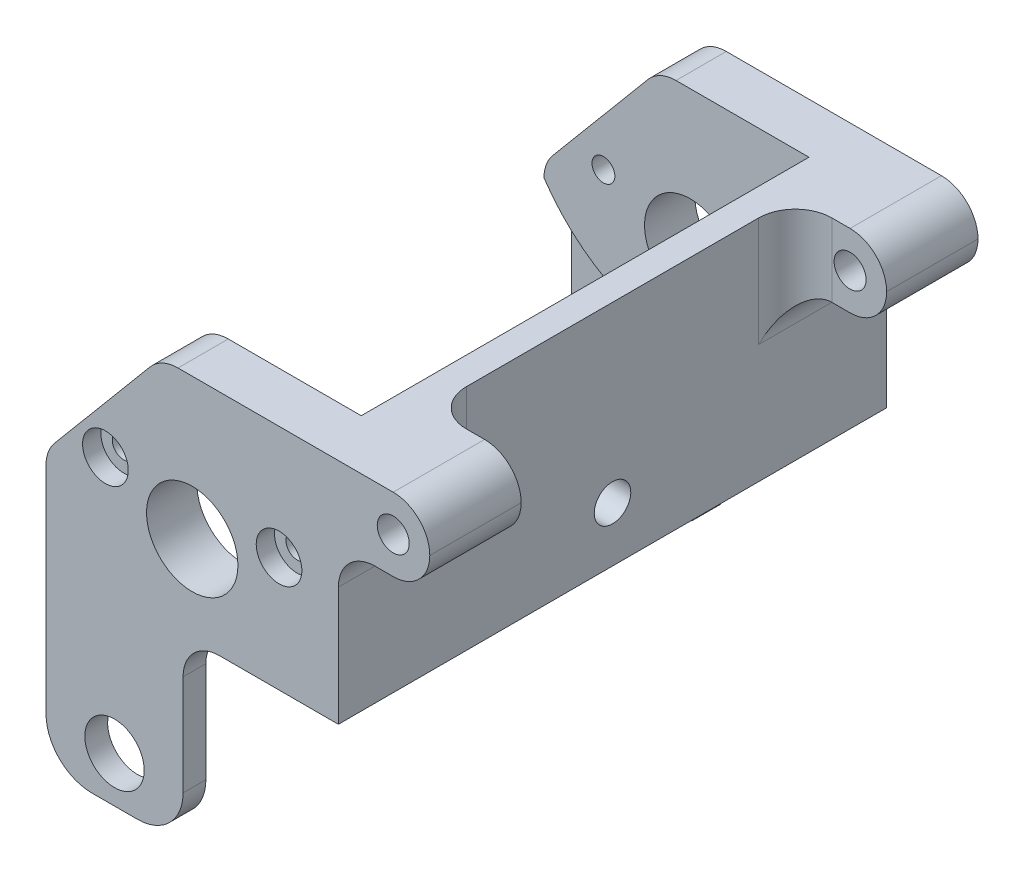
SolidWorks part; units mm, degrees
ref_plane "Front Plane" through (0, 0, 0) normal (0, 0, 1) x (1, 0, 0)
ref_plane "Top Plane" through (0, 0, 0) normal (0, 1, 0) x (1, 0, 0)
ref_plane "Right Plane" through (0, 0, 0) normal (1, 0, 0) x (0, 0, -1)
sketch "Sketch2" plane through (0, 0, 0) normal (0, 0, 1) x (1, 0, 0)
  line L0 (-7.5, 5) -> (-7.5, 30)
  line L1 (-7.5, 30) -> (5.0865, 45)
  line L2 (5.0865, 45) -> (24.5, 45)
  line L3 (24.5, 45) -> (24.5, 20)
  line L4 (24.5, 20) -> (7.5, 20)
  line L5 (7.5, 20) -> (7.5, 5)
  line L6 (-2.5, 0) -> (2.5, 0)
  line L7 (-7.5, 0) -> (7.5, 0) construction
  line L8 (-7.5, 5) -> (7.5, 5) construction
  line L9 (18.0048, 32.5697) -> (-0.9952, 32.5697) construction
  line L10 (8.5048, 32.5697) -> (8.5048, 29.5697) construction
  line L11 (0, 5) -> (8.5048, 29.5697) construction
  circle A5 centre (0, 5) radius 3.25
  circle A6 centre (18.0048, 32.5697) radius 1.25
  circle A7 centre (-0.9952, 32.5697) radius 1.25
  circle A8 centre (8.5048, 29.5697) radius 5
  circle A9 centre (8.5048, 32.5697) radius 12.5 construction
  arc A10 (2.5, 0) -> (7.5, 5) centre (2.5, 5) ccw
  arc A11 (-7.5, 5) -> (-2.5, 0) centre (-2.5, 5) ccw
  dimension "D3" = 6.5
  dimension "D4" = 5
  dimension "D10" = 10
  dimension "D12" = 2.5
  dimension "D14" = 25
  dimension "D15" = 5
  dimension "D1" = 40
  dimension "D2" = 15
  dimension "D5" = 30
  dimension "D6" = 15
  dimension "D7" = 17
  dimension "D8" = 20
  dimension "D9" = 19
  dimension "D11" = 3
  dimension "D13" = 26
extrude "Boss-Extrude1" add sketch "Sketch2" along normal blind 30 and the other way blind 30
sketch "Sketch3" plane through (0, 45, 0) normal (0, 1, 0) x (1, 0, 0)
  line L0 (-7.5, -30) -> (-7.5, 30) construction
  line L1 (-36.5, -27.5) -> (21.5, -27.5)
  line L2 (-36.5, -27.5) -> (-36.5, 27.5)
  line L3 (-36.5, 27.5) -> (21.5, 27.5)
  line L4 (21.5, -27.5) -> (21.5, 27.5)
  line L5 (-36.5, -27.5) -> (21.5, 27.5) construction
  line L6 (-36.5, 27.5) -> (21.5, -27.5) construction
  line L7 (24.5, 30) -> (5.0865, 30) construction
  line L8 (24.5, -30) -> (24.5, 30) construction
  point P0 (-7.5, 0)
  dimension "D1" = 2.5
  dimension "D2" = 3
extrude "Cut-Extrude1" cut sketch "Sketch3" against normal through all
sketch "Sketch4" plane through (24.5, 0, 0) normal (1, 0, 0) x (0, 0, -1)
  line L1 (-30, 45) -> (-20, 45)
  line L2 (-30, 45) -> (-30, 37)
  line L3 (-30, 37) -> (-20, 37)
  line L4 (-20, 45) -> (-20, 37)
  dimension "D1" = 10
  dimension "D2" = 8
extrude "Boss-Extrude2" add sketch "Sketch4" along normal blind 10
fillet "Fillet1" radius 4 2 edges at (34.5, 37, 25) (34.5, 45, 25)
sketch "Sketch5" plane through (0, 0, 20) normal (0, 0, -1) x (-1, 0, 0)
  circle A0 centre (-30.5, 41) radius 1.75
  dimension "D1" = 3.5
extrude "Cut-Extrude2" cut sketch "Sketch5" against normal through all
mirror "Mirror1" about plane through (0, 0, 0) normal (0, 0, 1) of "Cut-Extrude2", "Fillet1", "Boss-Extrude2"
fillet "Fillet2" radius 4 10 edges at (24.5, 41, -20) (24.5, 41, 20) (5.0865, 45, -28.75) (7.5, 20, -28.75) (24.5, 37, -25) (24.5, 37, 25) (7.5, 20, 28.75) (5.0865, 45, 28.75) (-7.5, 30, 28.75) (-7.5, 30, -28.75)
sketch "Sketch6" plane through (0, 0, -27.5) normal (0, 0, 1) x (1, 0, 0)
  line L0 (-0.9952, 32.5697) -> (18.0048, 32.5697) construction
  line L7 (21.5, 45) -> (6.9517, 45)
  line L8 (3.8875, 43.5712) -> (-6.5642, 31.1153)
  line L9 (-7.5, 28.5441) -> (-7.5, 5)
  line L10 (-2.5, 0) -> (2.5, 0)
  line L11 (7.5, 5) -> (7.5, 16)
  line L12 (11.5, 20) -> (21.5, 20)
  line L13 (21.5, 20) -> (21.5, 45)
  line L14 (21.5, 45) -> (6.9517, 45)
  line L15 (3.8875, 43.5712) -> (-6.5642, 31.1153)
  line L19 (11.5, 20) -> (21.5, 20)
  line L20 (21.5, 20) -> (21.5, 45)
  arc A1 (11.5, 20) -> (-7.5, 28.5441) centre (8.8465, 39.497) cw
  circle A2 centre (18.0048, 32.5697) radius 1.25 construction
  circle A3 centre (8.5048, 29.5697) radius 5 construction
  circle A4 centre (-0.9952, 32.5697) radius 1.25 construction
  circle A5 centre (18.0048, 32.5697) radius 1.25
  arc A6 (6.9517, 45) -> (3.8875, 43.5712) centre (6.9517, 41) ccw
  arc A7 (-6.5642, 31.1153) -> (-7.5, 28.5441) centre (-3.5, 28.5441) ccw
  arc A8 (-7.5, 5) -> (-2.5, 0) centre (-2.5, 5) ccw
  arc A9 (2.5, 0) -> (7.5, 5) centre (2.5, 5) ccw
  arc A10 (11.5, 20) -> (7.5, 16) centre (11.5, 16) ccw
  arc A11 (6.9517, 45) -> (3.8875, 43.5712) centre (6.9517, 41) ccw
  arc A12 (-6.5642, 31.1153) -> (-7.5, 28.5441) centre (-3.5, 28.5441) ccw
  circle A16 centre (8.5048, 29.5697) radius 5
  circle A17 centre (-0.9952, 32.5697) radius 1.25
  dimension "D1" = 0
extrude "Boss-Extrude3" add sketch "Sketch6" along normal blind 3
sketch "Sketch7" plane through (0, 0, -30) normal (0, 0, -1) x (-1, 0, 0)
  circle A0 centre (-18.0048, 32.5697) radius 2.5
  circle A1 centre (0.9952, 32.5697) radius 2.5
  dimension "D1" = 5
extrude "Cut-Extrude3" cut sketch "Sketch7" against normal blind 2
mirror "Mirror2" about plane through (0, 0, 0) normal (0, 0, 1) of "Cut-Extrude3", "Boss-Extrude3"
sketch "Sketch8" plane through (21.5, 0, 0) normal (-1, 0, 0) x (0, 0, 1)
  line L0 (0, 26) -> (0, 45) construction
  line L1 (24.5, 45) -> (-24.5, 45) construction
  circle A0 centre (0, 26) radius 2
  dimension "D1" = 4
  dimension "D2" = 19
extrude "Cut-Extrude4" cut sketch "Sketch8" against normal through all
